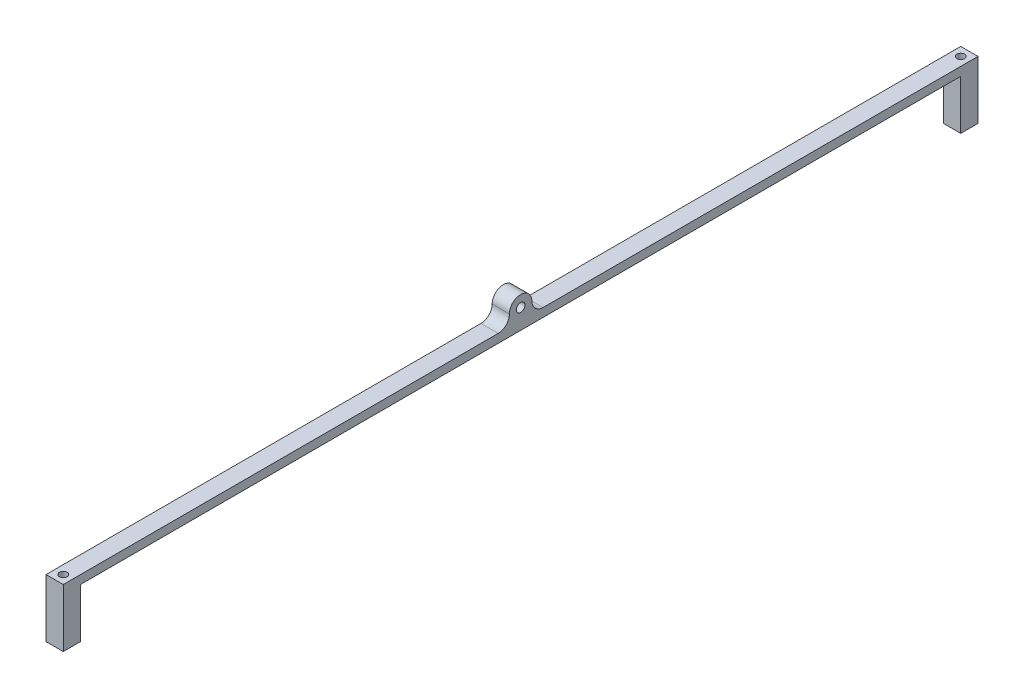
SolidWorks part; units mm, degrees
ref_plane "Спереди" through (0, 0, 0) normal (0, 0, 1) x (1, 0, 0)
ref_plane "Сверху" through (0, 0, 0) normal (0, 1, 0) x (1, 0, 0)
ref_plane "Справа" through (0, 0, 0) normal (1, 0, 0) x (0, 0, -1)
other "Configuration Table"
sketch "Эскиз1" plane through (0, 0, 0) normal (0, 1, 0) x (1, 0, 0)
  line L1 (0, 530) -> (10, 530)
  line L2 (0, 530) -> (0, 0)
  line L3 (0, 0) -> (10, 0)
  line L4 (10, 530) -> (10, 0)
  line L5 (592.3, 530) -> (592.3, 0) construction
  line L7 (0, 520) -> (10, 530) construction
  line L10 (0, 520) -> (10, 520) construction
  line L14 (0, 10) -> (10, 10) construction
  line L16 (0, 530) -> (10, 520) construction
  line L17 (0, 10) -> (10, 0) construction
  line L18 (10, 10) -> (0, 0) construction
  circle A0 centre (5, 525) radius 2.25
  circle A1 centre (5, 5) radius 2.25
  dimension "D5" = 4.5
  dimension "D6" = 4.5
  dimension "D2" = 10
  dimension "D3" = 10
  dimension "D4" = 10
extrude "Бобышка-Вытянуть1" add sketch "Эскиз1" along normal blind 5
sketch "Эскиз2" plane through (0, 0, 0) normal (1, 0, 0) x (0, 0, -1)
  line L0 (258.5, 11.5) -> (271.5, 11.5) construction
  line L1 (252, 5) -> (278, 5)
  line L2 (0, 5) -> (530, 5) construction
  arc A0 (271.5, 11.5) -> (258.5, 11.5) centre (265, 11.5) ccw
  arc A2 (252, 5) -> (258.5, 11.5) centre (252, 11.5) ccw
  arc A3 (271.5, 11.5) -> (278, 5) centre (278, 11.5) ccw
  circle A4 centre (265, 11.5) radius 2.5
  point P1 (265, 5)
  point P5 (265, 5)
  point P6 (271.5, 11.5)
  point P7 (258.5, 11.5)
  dimension "D1" = 13
  dimension "D2" = 13
  dimension "D3" = 13
  dimension "D4" = 5
extrude "Бобышка-Вытянуть2" add sketch "Эскиз2" along normal blind 10
sketch "Эскиз3" plane through (0, 0, 0) normal (0, -1, 0) x (1, 0, 0)
  line L0 (10, 0) -> (10, -530) construction
  line L1 (0, 0) -> (10, 0)
  line L2 (0, 0) -> (0, -10)
  line L3 (0, -10) -> (10, -10)
  line L4 (10, 0) -> (10, -10)
  line L6 (0, -530) -> (10, -530)
  line L7 (0, -530) -> (0, -520)
  line L8 (0, -520) -> (10, -520)
  line L9 (10, -530) -> (10, -520)
  circle A526 centre (5, -525) radius 2.25
  circle A527 centre (5, -525) radius 2.25
  circle A529 centre (5, -5) radius 2.25
  circle A530 centre (5, -5) radius 2.25
  dimension "D1" = 10
  dimension "D2" = 10
  dimension "D3" = 0
  dimension "D4" = 0
extrude "Бобышка-Вытянуть3" add sketch "Эскиз3" along normal up to surface (28.65 mm away)
